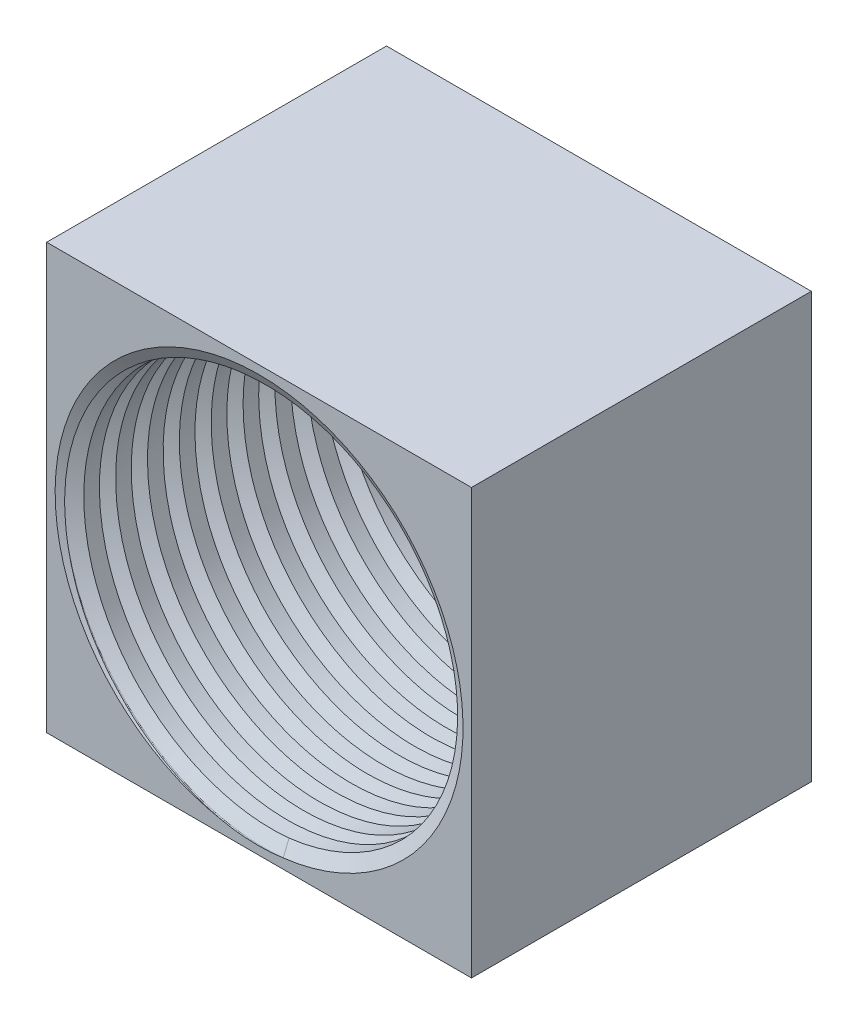
SolidWorks part; units mm, degrees
ref_plane "Front Plane" through (0, 0, 0) normal (0, 0, 1) x (1, 0, 0)
ref_plane "Top Plane" through (0, 0, 0) normal (0, 1, 0) x (1, 0, 0)
ref_plane "Right Plane" through (0, 0, 0) normal (1, 0, 0) x (0, 0, -1)
sketch "Sketch1" plane through (0, 0, 0) normal (0, 0, 1) x (1, 0, 0)
  line L1 (0, 0) -> (10, 0)
  line L2 (0, 0) -> (0, 10)
  line L3 (0, 10) -> (10, 10)
  line L4 (10, 0) -> (10, 10)
  dimension "D1" = 10
  dimension "D2" = 10
extrude "Boss-Extrude1" add sketch "Sketch1" along normal blind 8
sketch "Sketch2" plane through (0, 0, 8) normal (0, 0, 1) x (1, 0, 0)
  line L0 (5, 5) -> (5, 10) construction
  line L1 (10, 10) -> (0, 10) construction
  line L2 (5, 5) -> (0, 5) construction
  line L3 (0, 10) -> (0, 0) construction
  line L4 (5, 5) -> (5, 0) construction
  line L5 (0, 0) -> (10, 0) construction
  circle A0 centre (5, 5) radius 4.5
  dimension "D1" = 9
extrude "Cut-Extrude1" cut sketch "Sketch2" against normal up to next
sketch "Sketch21" plane through (0, 0, 8) normal (0, 0, 1) x (1, 0, 0)
  circle A0 centre (5, 5) radius 4.5 construction
  circle A1 centre (5, 5) radius 4.5
curve "Helix/Spiral8" pitch 0.75 height 8.25 radius 4.5 centre (5, 5, 8) axis (0, 0, -1) start towards (1, 0, 0)
ref_plane "Plane5" through (0, 5, 0) normal (0, -1, 0) x (-1, 0, 0)
sketch "Sketch22" plane through (0, 5, 0) normal (0, -1, 0) x (-1, 0, 0)
  line L0 (-10, -8) -> (-10, 0) construction
  line L1 (-9.5, -8.3822) -> (-9.5, -8)
  line L2 (-9.5, -8) -> (-9.801, -8.1738)
  line L3 (-9.801, -8.2084) -> (-9.5, -8.3822)
  line L4 (-9.7207, -8.1911) -> (-9.7207, -8.2548) construction
  line L5 (-9.7207, -8.1911) -> (-9.7207, -8.1274) construction
  line L7 (-9.5, -8.1911) -> (-9.811, -8.1911) construction
  circle A0 centre (-9.6103, -8.1911) radius 0.1103 construction
  arc A1 (-9.801, -8.2084) -> (-9.801, -8.1738) centre (-9.791, -8.1911) cw
  dimension "D2" = 0.02
  dimension "D1" = 0.311
sweep "Cut-Sweep9" cut profiles "Sketch22" path "Helix/Spiral8"
sketch "Sketch24" plane through (0, 0, 8) normal (0, 0, 1) x (1, 0, 0)
  circle A0 centre (5, 5) radius 4.801
extrude "Cut-Extrude2" cut sketch "Sketch24" against normal blind 10 draft 60
sketch "Sketch25" plane through (0, 0, 0) normal (0, 0, -1) x (-1, 0, 0)
  circle A0 centre (-5, 5) radius 4.801
extrude "Cut-Extrude3" cut sketch "Sketch25" against normal blind 10 draft 60
